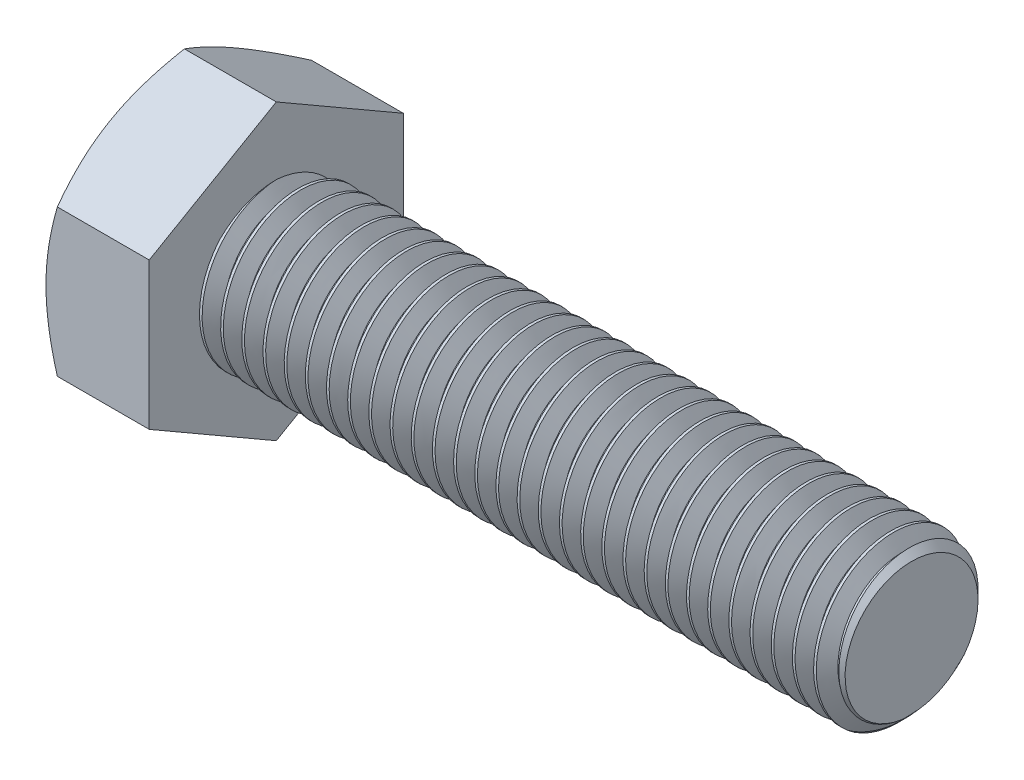
SolidWorks part; units mm, degrees
ref_plane "Front Plane" through (0, 0, 0) normal (0, 0, 1) x (1, 0, 0)
ref_plane "Top Plane" through (0, 0, 0) normal (0, 1, 0) x (1, 0, 0)
ref_plane "Right Plane" through (0, 0, 0) normal (1, 0, 0) x (0, 0, -1)
sketch "Sketch1" plane through (0, 0, 0) normal (0, 0, 1) x (1, 0, 0)
  line L0 (-18.4547, 0) -> (18.4547, 0) construction
  line L1 (18.4547, 3.9688) -> (18.4547, -3.9688) construction
  line L2 (-13.2953, 6.35) -> (-13.2953, -6.35) construction
  line L3 (-18.4547, 6.35) -> (-18.4547, -6.35) construction
  point P9 (-13.2953, 0)
  point P10 (14.7505, -3.9688)
  dimension "Screw Dia" = 7.9375
  dimension "Hex" = 12.7
  dimension "Head Ht" = 5.1594
  dimension "Screw Lenght" = 31.75
  dimension "D1" = 3.7042
ref_plane "Plane2" through (18.4547, 0, 0) normal (1, 0, 0) x (0, 0, -1)
sketch "Sketch5" plane through (18.4547, 0, 0) normal (1, 0, 0) x (0, 0, -1)
  circle A0 centre (0, 0) radius 3.9688
extrude "Boss-Extrude3" add sketch "Sketch5" against normal up to vertex (31.75 mm away) up to point (-13.2953, 0, 0)
sketch "Sketch9" plane through (18.4547, 0, 0) normal (1, 0, 0) x (0, 0, -1)
  circle A1 centre (0, 0) radius 3.9688
  circle A2 centre (0, 0) radius 3.9688
  dimension "D1" = 0
curve "Helix/Spiral1" pitch 1.0583 height 32.8083 turns 31 parameters "Pitch"=1.0583
chamfer "Chamfer1" distance 0.6477 angle 45 1 edges at (18.4547, 0, -3.9688)
sketch "Sketch10" plane through (0, 0, 0) normal (0, 0, 1) x (1, 0, 0)
  line L0 (18.4547, 3.9688) -> (18.8516, 3.2813)
  line L1 (18.8516, 3.2813) -> (18.9839, 3.2813)
  line L2 (18.9839, 3.2813) -> (19.3807, 3.9688)
  line L3 (18.4547, 3.9688) -> (19.3807, 3.9688)
  line L4 (18.9177, 3.9688) -> (18.9177, 3.2813) construction
  line L5 (18.6531, 3.625) -> (19.1823, 3.625) construction
  dimension "D1" = 60
  dimension "D2" = 0.1323
  dimension "D3" = 0.5292
sweep "Cut-Sweep1" cut profiles "Sketch10" path "Helix/Spiral1"
sketch "Sketch6" plane through (-13.2953, 0, 0) normal (-1, 0, 0) x (0, 0, 1)
  line L0 (0, 6.35) -> (0, -6.35) construction
  line L1 (6.35, 3.6662) -> (0, 7.3323)
  line L2 (0, 7.3323) -> (-6.35, 3.6662)
  line L3 (-6.35, 3.6662) -> (-6.35, -3.6662)
  line L4 (-6.35, -3.6662) -> (0, -7.3323)
  line L5 (0, -7.3323) -> (6.35, -3.6662)
  line L6 (6.35, -3.6662) -> (6.35, 3.6662)
  circle A0 centre (0, 0) radius 6.35 construction
extrude "Boss-Extrude4" add sketch "Sketch6" along normal up to vertex (5.1594 mm away) up to point (-18.4547, -6.35, 0)
sketch "Sketch7" plane through (-18.4547, 0, 0) normal (-1, 0, 0) x (0, 0, 1)
  circle A0 centre (0, 0) radius 6.35 construction
  circle A1 centre (0, 0) radius 6.35
sketch "Sketch8" plane through (-18.4547, 0, 0) normal (-1, 0, 0) x (0, 0, 1)
  circle A0 centre (0, 0) radius 6.35 construction
  circle A1 centre (0, 0) radius 6.35
extrude "Cut-Extrude3" cut sketch "Sketch8" against normal through all draft 60 flip side to cut
sketch "Sketch12" plane through (-18.4547, 0, 0) normal (-1, 0, 0) x (0, 0, 1)
  line L0 (0, 4.8895) -> (0, 2.7305) construction
  line L1 (0.1905, 4.8895) -> (0.1905, 2.7305)
  line L2 (-0.1905, 4.8895) -> (-0.1905, 2.7305)
  line L3 (0, 3.9688) -> (0, -3.9688) construction
  arc A0 (0.1905, 4.8895) -> (-0.1905, 4.8895) centre (0, 4.8895) ccw
  arc A1 (-0.1905, 2.7305) -> (0.1905, 2.7305) centre (0, 2.7305) ccw
  circle A3 centre (0, 0) radius 2.54 construction
  circle A4 centre (0, 0) radius 5.08 construction
  point P2 (0, 3.81)
  dimension "D1" = 5.08
  dimension "D3" = 10.16
  dimension "D2" = 0.381
extrude "Cut-Extrude4" cut sketch "Sketch12" against normal blind 0.254
pattern_circular "CirPattern1" count 3 over 360 about axis through (0, 0, 0) along (1, 0, 0) of "Cut-Extrude4"
equation "\"D2@Sketch10\" = \"Pitch@Helix/Spiral1\"*.125"
equation "\"D3@Sketch10\" = \"Pitch@Helix/Spiral1\"*.5"
equation "\"D1@Chamfer1\" = \"Pitch@Helix/Spiral1\"*.612"
equation "\"D1@Sketch12\" = \"Hex@Sketch1\"*.4"
equation "\"D3@Sketch12\" = \"Hex@Sketch1\"*.8"
equation "\"D2@Sketch12\" = \"Hex@Sketch1\"*.03"
equation "\"D1@Sketch1\" = \"Pitch@Helix/Spiral1\"*3.5"
equation "\"D3@Helix/Spiral1\" = \"Screw Lenght@Sketch1\"+\"Pitch@Helix/Spiral1\""
